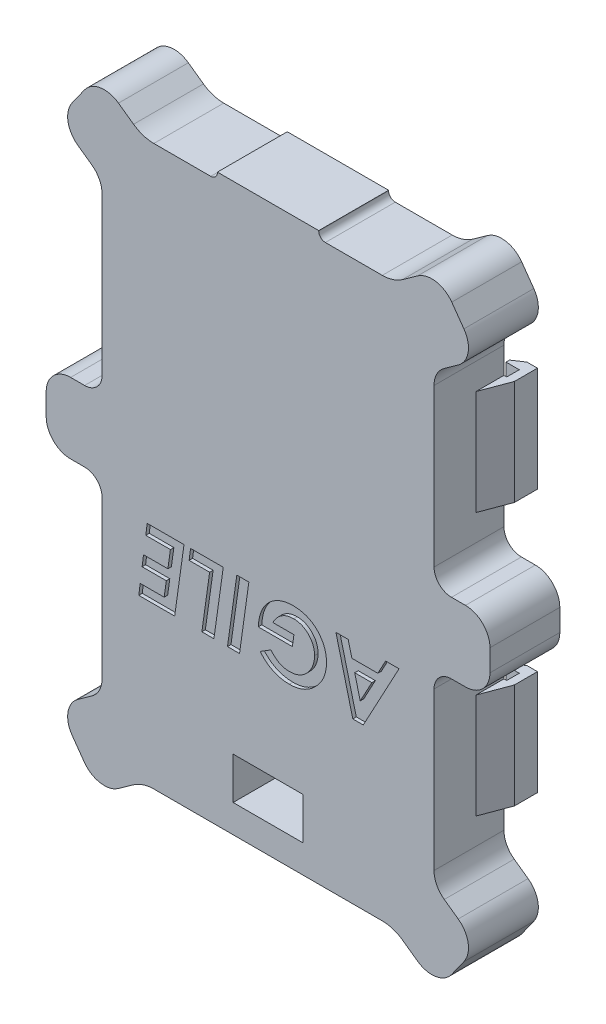
SolidWorks part; units mm, degrees
ref_plane "Front Plane" through (0, 0, 0) normal (0, 0, 1) x (1, 0, 0)
ref_plane "Top Plane" through (0, 0, 0) normal (0, 1, 0) x (1, 0, 0)
ref_plane "Right Plane" through (0, 0, 0) normal (1, 0, 0) x (0, 0, -1)
sketch "Sketch1" plane through (0, 0, 0) normal (0, 0, 1) x (1, 0, 0)
  line L0 (31.9975, -110.362) -> (31.9975, -120.362) construction
  line L1 (-24.4982, 18.6863) -> (-28.8129, 21.7633)
  line L2 (-42.0602, 15.2434) -> (-38.5765, 20.1284)
  line L3 (-36.4405, 2.638) -> (-40.4254, 5.4798)
  line L4 (-33.5049, -3.0612) -> (-33.5049, -48.0612)
  line L5 (-42.5049, -53.0612) -> (-38.5049, -53.0612)
  line L6 (43, -55.362) -> (43, -105.362) construction
  line L7 (-49.5049, -66.2828) -> (-49.5049, -60.0612)
  line L8 (-42.5049, -66.2828) -> (-42.5049, -71.7828) construction
  line L9 (0.9975, 17.328) -> (26.9975, 17.328)
  line L10 (70.5, -73.2828) -> (70.5, -71.7828) construction
  line L11 (77.5, -66.2828) -> (76, -66.2828) construction
  line L12 (70.5, -53.0612) -> (66.5, -53.0612)
  line L13 (61.5, -3.0612) -> (61.5, -48.0612)
  line L14 (64.4356, 2.638) -> (68.4204, 5.4798)
  line L15 (70.0553, 15.2434) -> (66.5716, 20.1284)
  line L16 (52.4933, 18.6863) -> (56.808, 21.7633)
  line L17 (-15.0049, -55.362) -> (-15.0049, -105.362) construction
  line L18 (52.4933, -145.0303) -> (56.808, -148.1073)
  line L19 (70.0553, -141.5874) -> (66.5716, -146.4724)
  line L20 (64.4356, -128.9821) -> (68.4204, -131.8238)
  line L21 (61.5, -123.2828) -> (61.5, -78.2828)
  line L22 (70.5, -73.2828) -> (66.5, -73.2828)
  line L23 (76, -66.2828) -> (76, -60.0612) construction
  line L24 (46.6871, -143.172) -> (-18.692, -143.172)
  line L25 (-42.5049, -66.2828) -> (-48.0049, -66.2828) construction
  line L26 (-42.5049, -73.2828) -> (-38.5049, -73.2828)
  line L27 (-33.5049, -123.2828) -> (-33.5049, -78.2828)
  line L28 (-36.4405, -128.9821) -> (-40.4254, -131.8238)
  line L29 (-42.0602, -141.5874) -> (-38.5765, -146.4724)
  line L30 (-24.4957, -145.0285) -> (-28.8129, -148.1073)
  line L31 (13.9975, -143.172) -> (13.9975, -125.172) construction
  line L32 (68.4204, 5.4798) -> (64.3561, 11.179) construction
  line L33 (33.9975, -34.362) -> (28.9975, -34.362) construction
  line L34 (28.9975, -34.362) -> (28.9975, -29.362) construction
  line L35 (-6.0025, 10.638) -> (-6.0025, -34.362) construction
  line L36 (33.9975, -34.362) -> (33.9975, -39.362) construction
  line L37 (33.9975, 10.638) -> (33.9975, -34.362) construction
  line L38 (30.3975, 16.828) -> (46.6871, 16.828)
  line L39 (26.9975, -39.362) -> (0.9975, -39.362) construction
  line L40 (26.9975, 18.828) -> (0.9975, 18.828)
  line L41 (64.3561, 11.179) -> (70.0553, 15.2434) construction
  line L42 (66.5716, 20.1284) -> (60.8724, 16.0641) construction
  line L43 (-6.0025, -34.362) -> (-6.0025, -50.362) construction
  line L44 (-6.0025, -50.362) -> (33.9975, -50.362) construction
  line L45 (33.9975, -50.362) -> (33.9975, -34.362) construction
  line L46 (31.9975, -50.362) -> (-4.0025, -50.362) construction
  line L47 (43, -55.362) -> (33.9975, -55.362) construction
  line L48 (26.9975, -48.362) -> (26.9975, -39.362) construction
  line L49 (-15.0049, -55.362) -> (-6.0025, -55.362) construction
  line L50 (0.9975, -48.362) -> (0.9975, -39.362) construction
  line L51 (31.9975, -110.362) -> (-4.0025, -110.362) construction
  line L52 (33.9975, -105.362) -> (43, -105.362) construction
  line L53 (31.9975, -120.362) -> (-4.0025, -120.362) construction
  line L54 (-6.0025, -34.362) -> (-1.0025, -34.362) construction
  line L55 (-4.0025, -120.362) -> (-4.0025, -110.362) construction
  line L56 (-1.0025, -34.362) -> (-1.0025, -29.362) construction
  line L57 (33.9975, 10.638) -> (28.9975, 10.638) construction
  line L58 (-6.0025, -105.362) -> (-15.0049, -105.362) construction
  line L59 (28.9975, 10.638) -> (28.9975, 5.638) construction
  line L60 (-6.0025, 10.638) -> (-1.0025, 10.638) construction
  line L61 (-1.0025, 10.638) -> (-1.0025, 5.638) construction
  line L62 (33.9975, -1.362) -> (33.9975, -22.362) construction
  line L63 (26.9975, -29.362) -> (0.9975, -29.362) construction
  line L64 (-6.0025, -22.362) -> (-6.0025, -1.362) construction
  line L65 (0.9975, 5.638) -> (26.9975, 5.638) construction
  line L66 (27.4975, -143.172) -> (0.4975, -143.172) construction
  line L67 (0.4975, -143.172) -> (0.4975, -136.172) construction
  line L68 (0.4975, -136.172) -> (27.4975, -136.172) construction
  line L69 (0.4975, -136.172) -> (0.4975, -125.172) construction
  line L70 (0.4975, -125.172) -> (27.4975, -125.172) construction
  line L71 (27.4975, -125.172) -> (27.4975, -136.172) construction
  line L72 (26.9975, -112.362) -> (26.9975, -120.362) construction
  line L73 (61.5, -78.2828) -> (43, -78.2828) construction
  line L74 (0.9975, -120.362) -> (0.9975, -112.362) construction
  line L75 (0.4975, -143.172) -> (0.4975, -113.172) construction
  line L76 (0.4975, -113.172) -> (27.4975, -113.172) construction
  line L77 (27.4975, -125.172) -> (24.4975, -125.172) construction
  line L78 (24.4975, -125.172) -> (24.4975, -134.172) construction
  line L79 (24.4975, -134.172) -> (3.4975, -134.172) construction
  line L80 (3.4975, -134.172) -> (3.4975, -125.172) construction
  line L81 (24.4975, -125.172) -> (24.4975, -134.172) construction
  line L82 (24.4975, -134.172) -> (3.4975, -134.172) construction
  line L83 (3.4975, -134.172) -> (3.4975, -125.172) construction
  line L84 (3.4975, -125.172) -> (0.9975, -120.362) construction
  line L85 (26.9975, -120.362) -> (24.4975, -125.172) construction
  line L86 (55.25, -78.2828) -> (49.25, -78.2828) construction
  line L87 (49.25, -78.2828) -> (49.25, -88.2828) construction
  line L88 (49.25, -88.2828) -> (55.25, -88.2828) construction
  line L89 (55.25, -88.2828) -> (55.25, -78.2828) construction
  line L90 (-15.0049, -78.2828) -> (-33.5049, -78.2828) construction
  line L91 (-21.2549, -78.2828) -> (-27.2549, -78.2828) construction
  line L92 (-27.2549, -78.2828) -> (-27.2549, -88.2828) construction
  line L93 (-27.2549, -88.2828) -> (-21.2549, -88.2828) construction
  line L94 (-21.2549, -88.2828) -> (-21.2549, -78.2828) construction
  line L95 (61.5, -3.0612) -> (43, -3.0612) construction
  line L96 (43, -3.0612) -> (43, -55.362) construction
  line L97 (55.25, -3.0612) -> (49.25, -3.0612) construction
  line L98 (49.25, -3.0612) -> (49.25, -13.0612) construction
  line L99 (49.25, -13.0612) -> (55.25, -13.0612) construction
  line L100 (55.25, -13.0612) -> (55.25, -3.0612) construction
  line L101 (-33.5049, -3.0612) -> (-15.0049, -3.0612) construction
  line L102 (-15.0049, -3.0612) -> (-15.0049, -55.362) construction
  line L103 (-21.2549, -3.0612) -> (-27.2549, -3.0612) construction
  line L104 (-27.2549, -3.0612) -> (-27.2549, -13.0612) construction
  line L105 (-27.2549, -13.0612) -> (-21.2549, -13.0612) construction
  line L106 (-21.2549, -13.0612) -> (-21.2549, -3.0612) construction
  line L107 (13.9975, -143.172) -> (13.9975, -135.172) construction
  line L108 (23.9975, -135.172) -> (3.9975, -135.172)
  line L109 (3.9975, -135.172) -> (3.9975, -123.172)
  line L110 (3.9975, -123.172) -> (23.9975, -123.172)
  line L111 (23.9975, -123.172) -> (23.9975, -135.172)
  line L112 (60.8724, -142.4081) -> (57.679, -146.886) construction
  line L113 (60.8724, -142.4081) -> (65.3503, -145.6015) construction
  line L114 (64.3561, -137.523) -> (68.4204, -131.8238) construction
  line L115 (64.3561, -137.523) -> (67.5495, -133.0451) construction
  line L116 (64.3561, -137.523) -> (68.8341, -140.7164) construction
  line L117 (65.3503, -145.6015) -> (68.8341, -140.7164)
  line L118 (52.4933, -145.0303) -> (54.501, -142.2149) construction
  line L119 (57.679, -146.886) -> (53.3642, -143.809)
  line L120 (46.6871, -143.172) -> (46.6871, -141.672) construction
  line L121 (46.6871, -141.672) -> (-18.6951, -141.672)
  line L122 (-18.692, -143.172) -> (-18.6951, -141.672) construction
  line L123 (-28.8129, -148.1073) -> (-40.4254, -131.8238) construction
  line L124 (-38.5765, -146.4724) -> (-32.8773, -142.4081) construction
  line L125 (-42.0602, -141.5874) -> (-36.361, -137.523) construction
  line L126 (-32.8773, -142.4081) -> (-29.6839, -146.886) construction
  line L127 (-32.8773, -142.4081) -> (-37.3552, -145.6015) construction
  line L128 (-36.361, -137.523) -> (-40.839, -140.7164) construction
  line L129 (-36.361, -137.523) -> (-39.5544, -133.0451) construction
  line L130 (-37.3552, -145.6015) -> (-40.839, -140.7164)
  line L131 (-29.6839, -146.886) -> (-25.3666, -143.8072)
  line L132 (-24.4957, -145.0285) -> (-25.3666, -143.8072) construction
  line L133 (-36.4405, -128.9821) -> (-35.5696, -130.2033) construction
  line L134 (-39.5544, -133.0451) -> (-35.5696, -130.2033)
  line L135 (-33.5049, -123.2828) -> (-32.0049, -123.2828) construction
  line L136 (-32.0049, -123.2828) -> (-32.0049, -78.2828)
  line L137 (-42.5049, -73.2828) -> (-42.5049, -53.0612) construction
  line L138 (-49.5049, -60.0612) -> (-42.5049, -60.0612) construction
  line L139 (-49.5049, -66.2828) -> (-42.5049, -66.2828) construction
  line L140 (-42.5049, -60.0612) -> (-42.5049, -54.5612) construction
  line L141 (-48.0049, -66.2828) -> (-48.0049, -60.0612)
  line L142 (-38.5049, -71.7828) -> (-42.5049, -71.7828)
  line L143 (-38.5049, -54.5612) -> (-42.5049, -54.5612) construction
  line L144 (-33.5049, -48.0612) -> (-32.0049, -48.0612)
  line L145 (-33.5049, -3.0612) -> (-32.0049, -3.0612)
  line L146 (-32.0049, -48.0612) -> (-32.0049, -3.0612)
  line L147 (-40.4254, 5.4798) -> (-36.361, 11.179) construction
  line L148 (-36.361, 11.179) -> (-42.0602, 15.2434) construction
  line L149 (-28.8129, 21.7633) -> (-32.8773, 16.0641) construction
  line L150 (-32.8773, 16.0641) -> (-38.5765, 20.1284) construction
  line L151 (-36.361, 11.179) -> (-38.0623, 8.7933) construction
  line L152 (-42.0602, 15.2434) -> (-40.839, 14.3724) construction
  line L153 (-40.4254, 5.4798) -> (-39.5544, 6.701) construction
  line L154 (-38.5765, 20.1284) -> (-37.3552, 19.2575) construction
  line L155 (-28.8129, 21.7633) -> (-29.6839, 20.542) construction
  line L156 (-36.4405, 2.638) -> (-35.5696, 3.8593) construction
  line L157 (-35.5696, 3.8593) -> (-39.5544, 6.701)
  line L158 (-40.839, 14.3724) -> (-37.3552, 19.2575)
  line L159 (-42.5049, -54.5612) -> (-38.5049, -54.5612)
  line L160 (-24.4982, 18.6863) -> (-25.3691, 17.465) construction
  line L161 (-29.6839, 20.542) -> (-25.3691, 17.465)
  line L162 (-18.692, 16.828) -> (-18.692, 15.328) construction
  line L163 (-18.692, 15.328) -> (0.9975, 15.328)
  line L164 (0.9975, 15.328) -> (0.9975, 17.328)
  line L165 (26.9975, 17.328) -> (26.9975, 15.328)
  line L166 (26.9975, 15.328) -> (46.6871, 15.328)
  line L167 (60.8724, 16.0641) -> (56.808, 21.7633) construction
  line L168 (-18.692, 16.828) -> (-2.4025, 16.828)
  line L169 (-0.5025, 18.728) -> (-0.5025, 18.828)
  line L170 (-0.5025, 18.828) -> (0.9975, 18.828)
  line L171 (28.4975, 18.728) -> (28.4975, 18.828)
  line L172 (28.4975, 18.828) -> (26.9975, 18.828)
  line L173 (64.3561, 11.179) -> (68.8341, 14.3724) construction
  line L174 (68.8341, 14.3724) -> (65.3503, 19.2575) construction
  line L175 (52.4933, 18.6863) -> (53.3642, 17.465) construction
  line L176 (57.679, 20.542) -> (53.3642, 17.465)
  line L177 (64.4356, 2.638) -> (63.5647, 3.8593) construction
  line L178 (63.5647, 3.8593) -> (67.5495, 6.701) construction
  line L179 (63.5647, 3.8593) -> (67.5495, 6.701)
  line L180 (67.5495, -133.0451) -> (63.5647, -130.2033) construction
  line L181 (61.5, -123.2828) -> (60, -123.2828) construction
  line L182 (60, -123.2828) -> (60, -78.2828)
  line L183 (66.5, -73.2828) -> (66.5, -71.7828) construction
  line L184 (66.5, -53.0612) -> (66.5, -54.5612) construction
  line L185 (61.5, -48.0612) -> (60, -48.0612) construction
  line L186 (61.5, -3.0612) -> (60, -3.0612) construction
  line L187 (77.5, -66.2828) -> (77.5, -60.0612)
  line L188 (76, -60.0612) -> (77.5, -60.0612) construction
  line L189 (70.5, -53.0612) -> (70.5, -54.5612) construction
  line L190 (66.5, -71.7828) -> (70.5, -71.7828)
  line L191 (76, -66.2828) -> (76, -60.0612)
  line L192 (70.5, -54.5612) -> (66.5, -54.5612)
  line L193 (60, -48.0612) -> (60, -3.0612)
  line L194 (76, -66.2828) -> (70.5, -66.2828) construction
  line L195 (70.5, -66.2828) -> (70.5, -71.7828) construction
  line L196 (76, -60.0612) -> (70.5, -60.0612) construction
  line L197 (70.5, -60.0612) -> (70.5, -54.5612) construction
  line L198 (67.5495, -133.0451) -> (63.5647, -130.2033)
  line L199 (68.8341, 14.3724) -> (65.3503, 19.2575)
  line L200 (3.9975, -123.172) -> (23.9975, -135.172) construction
  line L201 (23.9975, -123.172) -> (3.9975, -135.172) construction
  line L203 (1.9975, -136.672) -> (25.9975, -136.672)
  line L204 (1.9975, -136.672) -> (1.9975, -121.672)
  line L205 (1.9975, -121.672) -> (25.9975, -121.672)
  line L206 (25.9975, -136.672) -> (25.9975, -121.672)
  line L207 (1.9975, -136.672) -> (25.9975, -121.672) construction
  line L208 (1.9975, -121.672) -> (25.9975, -136.672) construction
  circle A0 centre (-37.998, 16.0311) radius 1 construction
  circle A1 centre (-29.6584, 17.5638) radius 1 construction
  circle A2 centre (-36.7303, 7.6471) radius 1 construction
  arc A3 (-38.5049, -53.0612) -> (-33.5049, -48.0612) centre (-38.5049, -48.0612) ccw
  arc A4 (-49.5049, -60.0612) -> (-42.5049, -53.0612) centre (-42.5049, -60.0612) cw
  circle A5 centre (-28.3907, 9.1798) radius 1 construction
  circle A6 centre (-33.1943, 12.6054) radius 3.5 construction
  arc A7 (-24.4982, 18.6863) -> (-18.692, 16.828) centre (-18.692, 26.828) ccw
  arc A8 (-40.4254, 5.4798) -> (-42.0602, 15.2434) centre (-36.361, 11.179) cw
  arc A9 (-38.5765, 20.1284) -> (-28.8129, 21.7633) centre (-32.8773, 16.0641) cw
  arc A10 (-33.5049, -3.0612) -> (-36.4405, 2.638) centre (-40.5049, -3.0612) ccw
  arc A11 (61.5, -3.0612) -> (64.4356, 2.638) centre (68.5, -3.0612) cw
  arc A12 (66.5716, 20.1284) -> (56.808, 21.7633) centre (60.8724, 16.0641) ccw
  arc A13 (68.4204, 5.4798) -> (70.0553, 15.2434) centre (64.3561, 11.179) ccw
  arc A14 (52.4933, 18.6863) -> (46.6871, 16.828) centre (46.6871, 26.828) cw
  circle A15 centre (61.1894, 12.6054) radius 3.5 construction
  circle A16 centre (56.3858, 9.1798) radius 1 construction
  arc A17 (77.5, -60.0612) -> (70.5, -53.0612) centre (70.5, -60.0612) ccw
  arc A18 (66.5, -53.0612) -> (61.5, -48.0612) centre (66.5, -48.0612) cw
  circle A19 centre (64.7254, 7.6471) radius 1 construction
  circle A20 centre (57.6534, 17.5638) radius 1 construction
  circle A21 centre (65.9931, 16.0311) radius 1 construction
  circle A22 centre (65.9931, -142.3751) radius 1 construction
  circle A23 centre (57.6534, -143.9078) radius 1 construction
  circle A24 centre (64.7254, -133.9911) radius 1 construction
  arc A25 (66.5, -73.2828) -> (61.5, -78.2828) centre (66.5, -78.2828) ccw
  arc A26 (77.5, -66.2828) -> (70.5, -73.2828) centre (70.5, -66.2828) cw
  circle A27 centre (56.3858, -135.5238) radius 1 construction
  circle A28 centre (61.1894, -138.9495) radius 3.5 construction
  arc A29 (52.4933, -145.0303) -> (46.6871, -143.172) centre (46.6871, -153.172) ccw construction
  arc A30 (68.4204, -131.8238) -> (70.0553, -141.5874) centre (64.3561, -137.523) cw
  arc A31 (66.5716, -146.4724) -> (56.808, -148.1073) centre (60.8724, -142.4081) cw
  arc A32 (61.5, -123.2828) -> (64.4356, -128.9821) centre (68.5, -123.2828) ccw
  arc A33 (-33.5049, -123.2828) -> (-36.4405, -128.9821) centre (-40.5049, -123.2828) cw
  arc A34 (-38.5765, -146.4724) -> (-28.8129, -148.1073) centre (-32.8773, -142.4081) ccw
  arc A35 (-40.4254, -131.8238) -> (-42.0602, -141.5874) centre (-36.361, -137.523) ccw
  arc A36 (-24.4957, -145.0285) -> (-18.692, -143.172) centre (-18.692, -153.172) cw
  circle A37 centre (-33.164, -138.172) radius 3.5 construction
  circle A38 centre (-28.3907, -135.5238) radius 1 construction
  arc A39 (-49.5049, -66.2828) -> (-42.5049, -73.2828) centre (-42.5049, -66.2828) ccw
  arc A40 (-38.5049, -73.2828) -> (-33.5049, -78.2828) centre (-38.5049, -78.2828) cw
  circle A41 centre (-36.7303, -133.9911) radius 1 construction
  circle A42 centre (-29.6584, -143.9078) radius 1 construction
  circle A43 centre (-37.998, -142.3751) radius 1 construction
  circle A44 centre (-6.0025, -34.362) radius 1.5 construction
  circle A45 centre (55.31, -25.5612) radius 1.5 construction
  circle A46 centre (33.9975, -136.982) radius 1.5 construction
  circle A47 centre (-6.0025, -136.982) radius 1.5 construction
  circle A48 centre (-6.0025, 10.638) radius 1.5 construction
  circle A49 centre (33.9975, 10.638) radius 1.5 construction
  circle A50 centre (33.9975, -34.362) radius 1.5 construction
  circle A51 centre (31.9975, -50.362) radius 1.5 construction
  circle A52 centre (-4.0025, -50.362) radius 1.5 construction
  arc A53 (-6.0025, -55.362) -> (0.9975, -48.362) centre (-6.0025, -48.362) ccw construction
  arc A54 (33.9975, -55.362) -> (26.9975, -48.362) centre (33.9975, -48.362) cw construction
  circle A55 centre (-4.0025, -110.362) radius 1.5 construction
  circle A56 centre (31.9975, -110.362) radius 1.5 construction
  arc A57 (0.9975, -112.362) -> (-6.0025, -105.362) centre (-6.0025, -112.362) ccw construction
  arc A58 (33.9975, -105.362) -> (26.9975, -112.362) centre (33.9975, -112.362) ccw construction
  arc A59 (33.9975, -22.362) -> (26.9975, -29.362) centre (26.9975, -22.362) cw construction
  circle A60 centre (-27.3149, -25.5612) radius 1.5 construction
  circle A61 centre (55.31, -100.7828) radius 1.5 construction
  circle A62 centre (-27.3149, -100.7828) radius 1.5 construction
  arc A63 (0.9975, -29.362) -> (-6.0025, -22.362) centre (0.9975, -22.362) cw construction
  arc A64 (-6.0025, -1.362) -> (0.9975, 5.638) centre (0.9975, -1.362) cw construction
  arc A65 (33.9975, -1.362) -> (26.9975, 5.638) centre (26.9975, -1.362) ccw construction
  circle A66 centre (27.4975, -136.172) radius 1 construction
  circle A67 centre (0.4975, -136.172) radius 1 construction
  circle A68 centre (27.4975, -125.172) radius 1 construction
  circle A69 centre (0.4975, -125.172) radius 1 construction
  arc A70 (53.3642, -143.809) -> (46.6871, -141.672) centre (46.6871, -153.172) ccw
  arc A71 (57.679, -146.886) -> (65.3503, -145.6015) centre (60.8724, -142.4081) ccw
  arc A72 (52.4933, -145.0303) -> (46.6871, -143.172) centre (46.6871, -153.172) ccw
  arc A73 (63.5647, -130.2033) -> (60, -123.2828) centre (68.5, -123.2828) cw
  circle A74 centre (-40.7503, -63.172) radius 3.5 construction
  circle A75 centre (-46.6503, -63.172) radius 1 construction
  circle A76 centre (-34.8503, -63.172) radius 1 construction
  circle A77 centre (-40.4873, -69.2563) radius 1 construction
  circle A78 centre (-40.4873, -57.0877) radius 1 construction
  circle A79 centre (68.4824, -57.0877) radius 1 construction
  circle A80 centre (68.4824, -69.2563) radius 1 construction
  circle A81 centre (62.8454, -63.172) radius 1 construction
  circle A82 centre (74.6454, -63.172) radius 1 construction
  circle A83 centre (68.7454, -63.172) radius 3.5 construction
  arc A84 (-37.3552, -145.6015) -> (-29.6839, -146.886) centre (-32.8773, -142.4081) ccw
  arc A85 (-18.6951, -141.672) -> (-25.3666, -143.8072) centre (-18.6951, -153.1623) ccw
  arc A86 (-40.839, -140.7164) -> (-39.5544, -133.0451) centre (-36.361, -137.523) cw
  arc A87 (-35.5696, -130.2033) -> (-32.0049, -123.2828) centre (-40.5049, -123.2828) ccw
  arc A88 (-32.0049, -78.2828) -> (-38.5049, -71.7828) centre (-38.5049, -78.2828) ccw
  arc A89 (-42.5049, -71.7828) -> (-48.0049, -66.2828) centre (-42.5049, -66.2828) cw
  arc A90 (-48.0049, -60.0612) -> (-42.5049, -54.5612) centre (-42.5049, -60.0612) cw
  arc A91 (-32.0049, -48.0612) -> (-38.5049, -54.5612) centre (-38.5049, -48.0612) cw
  arc A92 (-32.0049, -3.0612) -> (-35.5696, 3.8593) centre (-40.5049, -3.0612) ccw
  arc A93 (-39.5544, 6.701) -> (-40.839, 14.3724) centre (-36.361, 11.179) cw
  arc A94 (-37.3552, 19.2575) -> (-29.6839, 20.542) centre (-32.8773, 16.0641) cw
  arc A95 (-25.3691, 17.465) -> (-18.692, 15.328) centre (-18.692, 26.828) ccw
  arc A96 (30.3975, 16.828) -> (28.4975, 18.728) centre (30.3975, 18.728) cw
  arc A97 (-0.5025, 18.728) -> (-2.4025, 16.828) centre (-2.4025, 18.728) cw
  arc A98 (67.5495, 6.701) -> (68.8341, 14.3724) centre (64.3561, 11.179) ccw
  arc A99 (65.3503, 19.2575) -> (57.679, 20.542) centre (60.8724, 16.0641) ccw
  arc A100 (46.6871, 15.328) -> (53.3642, 17.465) centre (46.6871, 26.828) ccw
  arc A101 (67.5495, -133.0451) -> (68.8341, -140.7164) centre (64.3561, -137.523) cw
  arc A102 (63.5647, 3.8593) -> (60, -3.0612) centre (68.5, -3.0612) ccw
  arc A103 (66.5, -54.5612) -> (60, -48.0612) centre (66.5, -48.0612) cw
  arc A104 (76, -60.0612) -> (70.5, -54.5612) centre (70.5, -60.0612) ccw
  arc A105 (76, -66.2828) -> (70.5, -71.7828) centre (70.5, -66.2828) cw
  arc A106 (66.5, -71.7828) -> (60, -78.2828) centre (66.5, -78.2828) ccw
  point P25 (-34.5122, 25.8276)
  point P29 (-34.5122, 25.8276)
  point P64 (62.5072, 25.8276)
  point P95 (62.5072, -152.1716)
  point P124 (-34.5122, -152.1716)
  point P144 (13.9975, 16.828)
  point P147 (13.9975, 16.828)
  point P154 (13.9975, -50.362)
  point P182 (13.9975, -125.172)
  point P196 (33.9975, -29.362)
  point P199 (-6.0025, -29.362)
  point P202 (-6.0025, 5.638)
  point P215 (33.9975, 5.638)
  point P229 (13.9975, -143.172)
  point P249 (52.25, -78.2828)
  point P256 (-24.2549, -78.2828)
  point P261 (52.25, -3.0612)
  point P267 (-24.2549, -3.0612)
  point P273 (13.9975, -135.172)
  point P358 (13.9975, -129.172)
  dimension "D6" = 7
  dimension "D7" = 7
  dimension "D10" = 6.7223
  dimension "D11" = 1.9
  dimension "D1" = 10
  dimension "D2" = 7
  dimension "D3" = 7
  dimension "D4" = 5
  dimension "D5" = 7
  dimension "D8" = 7
  dimension "D9" = 5.4953
extrude "Бобышка-Вытянуть3" add sketch "Sketch1" along normal blind 18 contours L190 A106 L182 A73 L198 A101 L117 A71 L119 A70 L121 A85 L131 A84 L130 A86 L134 A87 L136 A88 L142 A89 L141 A90 L159 A91 L144 A3 L5 A4 L7 A39 L26 A40 L27 A33 L28 A35 L29 A34 L30 A36 L24 A72 L18 A31 L19 A30 L20 A32 L21 | L144 L146 L145 L4 | L203 L206 L205 L204 L110 L111 L108 L109 region at (-21.8054, 17.0999, 0) region at (-32.7549, -25.5612, 0) region at (2.2806, -129.172, 0)
sketch "Эскиз1" plane through (0, 0, 18) normal (0, 0, 1) x (1, 0, 0)
  line L0 (66.5, -53.0612) -> (70.5, -53.0612)
  line L6 (3.9975, -135.172) -> (23.9975, -135.172)
  line L7 (3.9975, -135.172) -> (3.9975, -123.172)
  line L8 (3.9975, -123.172) -> (23.9975, -123.172)
  line L10 (23.9975, -135.172) -> (23.9975, -123.172)
  line L11 (3.9975, -135.172) -> (23.9975, -123.172) construction
  line L12 (3.9975, -123.172) -> (23.9975, -135.172) construction
  line L25 (46.6871, -141.672) -> (-18.6951, -141.672)
  line L30 (61.5, -123.2828) -> (61.5, -78.2828)
  line L31 (66.5, -73.2828) -> (70.5, -73.2828)
  line L32 (77.5, -66.2828) -> (77.5, -60.0612)
  line L35 (61.5, -48.0612) -> (61.5, -3.0612)
  line L36 (64.4356, 2.638) -> (68.4204, 5.4798)
  line L37 (70.0553, 15.2434) -> (66.5716, 20.1284)
  line L38 (56.808, 21.7633) -> (52.4933, 18.6863)
  line L39 (46.6871, 16.828) -> (30.3975, 16.828)
  line L40 (28.4975, 18.828) -> (-0.5025, 18.828)
  line L41 (-0.5025, 18.828) -> (-0.5025, 18.728)
  line L42 (28.4975, 18.728) -> (28.4975, 18.828)
  line L43 (-2.4025, 16.828) -> (-18.692, 16.828)
  line L44 (-24.4982, 18.6863) -> (-28.8129, 21.7633)
  line L45 (-38.5765, 20.1284) -> (-42.0602, 15.2434)
  line L46 (-40.4254, 5.4798) -> (-36.4405, 2.638)
  line L47 (-33.5049, -3.0612) -> (-33.5049, -48.0612)
  line L48 (-38.5049, -53.0612) -> (-42.5049, -53.0612)
  line L49 (-49.5049, -60.0612) -> (-49.5049, -66.2828)
  line L50 (-42.5049, -73.2828) -> (-38.5049, -73.2828)
  line L51 (-33.5049, -78.2828) -> (-33.5049, -123.2828)
  line L52 (-36.4405, -128.9821) -> (-40.4254, -131.8238)
  line L53 (-42.0602, -141.5874) -> (-38.5765, -146.4724)
  line L54 (-28.8129, -148.1073) -> (-24.4957, -145.0285)
  line L55 (-18.692, -143.172) -> (46.6871, -143.172)
  line L56 (56.808, -148.1073) -> (52.4933, -145.0303)
  line L57 (66.5716, -146.4724) -> (70.0553, -141.5874)
  line L58 (68.4204, -131.8238) -> (64.4356, -128.9821)
  arc A2 (61.5, -123.2828) -> (64.4356, -128.9821) centre (68.5, -123.2828) ccw construction
  arc A3 (-33.5049, -78.2828) -> (-38.5049, -73.2828) centre (-38.5049, -78.2828) ccw construction
  arc A4 (70.0553, -141.5874) -> (68.4204, -131.8238) centre (64.3561, -137.523) ccw
  arc A5 (-42.0602, -141.5874) -> (-40.4254, -131.8238) centre (-36.361, -137.523) cw
  arc A6 (-36.4405, -128.9821) -> (-33.5049, -123.2828) centre (-40.5049, -123.2828) ccw
  arc A7 (56.808, -148.1073) -> (66.5716, -146.4724) centre (60.8724, -142.4081) ccw
  arc A8 (46.6871, -143.172) -> (52.4933, -145.0303) centre (46.6871, -153.172) cw
  arc A9 (-38.5765, -146.4724) -> (-28.8129, -148.1073) centre (-32.8773, -142.4081) ccw
  arc A10 (-24.4957, -145.0285) -> (-18.692, -143.172) centre (-18.692, -153.172) cw
  arc A11 (64.4356, -128.9821) -> (61.5, -123.2828) centre (68.5, -123.2828) cw
  arc A12 (61.5, -78.2828) -> (66.5, -73.2828) centre (66.5, -78.2828) cw
  arc A13 (70.5, -73.2828) -> (77.5, -66.2828) centre (70.5, -66.2828) ccw
  arc A14 (77.5, -60.0612) -> (70.5, -53.0612) centre (70.5, -60.0612) ccw
  arc A15 (66.5, -53.0612) -> (61.5, -48.0612) centre (66.5, -48.0612) cw
  arc A16 (61.5, -3.0612) -> (64.4356, 2.638) centre (68.5, -3.0612) cw
  arc A17 (68.4204, 5.4798) -> (70.0553, 15.2434) centre (64.3561, 11.179) ccw
  arc A18 (66.5716, 20.1284) -> (56.808, 21.7633) centre (60.8724, 16.0641) ccw
  arc A19 (52.4933, 18.6863) -> (46.6871, 16.828) centre (46.6871, 26.828) cw
  arc A20 (28.4975, 18.728) -> (30.3975, 16.828) centre (30.3975, 18.728) ccw
  arc A21 (-18.692, 16.828) -> (-24.4982, 18.6863) centre (-18.692, 26.828) cw
  arc A22 (-2.4025, 16.828) -> (-0.5025, 18.728) centre (-2.4025, 18.728) ccw
  arc A23 (-38.5765, 20.1284) -> (-28.8129, 21.7633) centre (-32.8773, 16.0641) cw
  arc A24 (-42.0602, 15.2434) -> (-40.4254, 5.4798) centre (-36.361, 11.179) ccw
  arc A25 (-36.4405, 2.638) -> (-33.5049, -3.0612) centre (-40.5049, -3.0612) cw
  arc A26 (-49.5049, -60.0612) -> (-42.5049, -53.0612) centre (-42.5049, -60.0612) cw
  arc A27 (-38.5049, -53.0612) -> (-33.5049, -48.0612) centre (-38.5049, -48.0612) ccw
  arc A28 (-49.5049, -66.2828) -> (-42.5049, -73.2828) centre (-42.5049, -66.2828) ccw
  arc A29 (-38.5049, -73.2828) -> (-33.5049, -78.2828) centre (-38.5049, -78.2828) cw
  point P52 (13.9975, -129.172)
  point P53 (13.9975, -129.172)
extrude "Бобышка-Вытянуть4" add sketch "Эскиз1" along normal blind 2 contours L50 A29 L51 A6 L52 A5 L53 A9 L54 A10 L55 A8 L56 A7 L57 A4 L58 A11 L30 A12 L31 A13 L32 A14 L0 A15 L35 A16 L36 A17 L37 A18 L38 A19 L39 A20 L42 L40 L41 A22 L43 A21 L44 A23 L45 A24 L46 A25 region at (13.9975, -61.9149, 18)
sketch "Эскиз2" plane through (0, 0, 0) normal (0, 0, -1) x (-1, 0, 0)
  line L1 (-1.9975, -136.672) -> (-25.9975, -136.672)
  line L2 (-1.9975, -136.672) -> (-1.9975, -121.672)
  line L3 (-1.9975, -121.672) -> (-25.9975, -121.672)
  line L4 (-25.9975, -136.672) -> (-25.9975, -121.672)
  line L5 (-1.9975, -136.672) -> (-25.9975, -121.672) construction
  line L6 (-1.9975, -121.672) -> (-25.9975, -136.672) construction
  line L7 (-3.9975, -135.172) -> (-23.9975, -135.172)
  line L8 (-3.9975, -135.172) -> (-3.9975, -123.172)
  line L9 (-3.9975, -123.172) -> (-23.9975, -123.172)
  line L10 (-23.9975, -135.172) -> (-23.9975, -123.172)
  line L11 (-3.9975, -135.172) -> (-23.9975, -123.172) construction
  line L12 (-3.9975, -123.172) -> (-23.9975, -135.172) construction
  point P4 (-13.9975, -129.172)
  point P11 (-13.9975, -129.172)
extrude "Вырез-Вытянуть1" cut sketch "Эскиз2" against normal blind 6
sketch "Эскиз3" plane through (0, -143.172, 0) normal (0, -1, 0) x (1, 0, 0)
  line L0 (41.6975, 0) -> (44.2975, 0)
  line L1 (13.9975, 0.2) -> (13.9975, 4.2) construction
  line L2 (-3.0025, 4.2) -> (30.9975, 4.2)
  line L3 (30.9975, 4.2) -> (30.9975, 0)
  line L4 (30.9975, 0) -> (-3.0025, 0)
  line L5 (-3.0025, 0) -> (-3.0025, 4.2)
  line L6 (-3.0025, 0) -> (-15.0025, 0) construction
  line L7 (30.9975, 0) -> (42.9975, 0) construction
  line L8 (46.6871, 0) -> (-18.692, 0) construction
  line L9 (44.2975, 0) -> (44.2975, 4)
  line L10 (41.6975, 0) -> (41.6975, 4)
  line L12 (-16.3025, 0) -> (-13.7025, 0)
  line L15 (-13.7025, 0) -> (-13.7025, 4)
  line L16 (-16.3025, 0) -> (-16.3025, 4)
  arc A0 (41.6975, 4) -> (44.2975, 4) centre (42.9975, 4) cw
  arc A2 (-13.7025, 4) -> (-16.3025, 4) centre (-15.0025, 4) ccw
  point P9 (13.9975, 4.2)
  point P14 (42.9975, 0)
  point P21 (-15.0025, 0)
  point P22 (-12.1059, 2.6062)
extrude "Вырез-Вытянуть2" cut sketch "Эскиз3" against normal blind 1.5
sketch "Эскиз4" plane through (0, 0, 20) normal (0, 0, 1) x (1, 0, 0)
  line L0 (61.5, -78.2828) -> (-33.5049, -78.2828) construction
  arc A0 (-33.5049, -78.2828) -> (-38.5049, -73.2828) centre (-38.5049, -78.2828) ccw construction
  text T0 "AGILE" font "Century Gothic" height in points 72
extrude "Вырез-Вытянуть3" cut sketch "Эскиз4" against normal blind 1
sketch "Эскиз5" plane through (-33.5049, 0, 0) normal (-1, 0, 0) x (0, 0, 1)
  line L0 (0, -25.5612) -> (0, -40.5612) construction
  line L2 (0, -100.7828) -> (0, -115.7828) construction
  line L4 (0, -100.7828) -> (0, -85.7828) construction
  line L8 (0, -3.0612) -> (0, -48.0612) construction
  line L9 (0, -40.5612) -> (0, -10.5612) construction
  line L10 (8, -10.5612) -> (-3.2, -10.5612)
  line L12 (-3.2, -40.5612) -> (8, -40.5612)
  line L13 (8, -40.5612) -> (8, -10.5612)
  line L14 (0, -123.2828) -> (0, -78.2828) construction
  line L15 (-3.2, -40.5612) -> (-3.2, -10.5612) construction
  line L21 (0, -85.7828) -> (8, -85.7828)
  line L22 (8, -85.7828) -> (8, -115.7828)
  line L23 (8, -115.7828) -> (-3.2, -115.7828)
  line L24 (-3.2, -115.7828) -> (-3.2, -85.7828) construction
  line L25 (-3.2, -85.7828) -> (0, -85.7828)
  line L26 (-3.2, -85.7828) -> (-6.2, -85.7828) construction
  line L27 (-3.2, -85.7828) -> (-6.2, -85.7828)
  line L28 (-6.2, -85.7828) -> (-6.2, -115.7828)
  line L29 (-6.2, -115.7828) -> (-3.4965, -115.7828)
  line L30 (-3.2, -40.5612) -> (-6.6, -40.5612)
  line L31 (-6.6, -40.5612) -> (-6.6, -10.5612)
  line L32 (-6.6, -10.5612) -> (-3.2, -10.5612)
  point P0 (0, -25.5612)
  point P4 (0, -100.7828)
  line M25 (0, -3.0612) -> (0, -48.0612)
extrude "Бобышка-Вытянуть5" add sketch "Эскиз5" along normal blind 3 contours L12 L13 L10 M25 | L32 L31 L30 L12 L10 M25 region at (-33.5049, -25.5612, 4) region at (-33.5049, -25.5612, -3.3)
sketch "Эскиз7" plane through (-33.5049, 0, 0) normal (1, 0, 0) x (0, 0, -1)
  line L0 (6.6, -10.5612) -> (3.6, -10.5612) construction
  line L1 (0, -10.5612) -> (6.6, -10.5612) construction
  line L2 (3.6, -10.5612) -> (6.6, -10.5612)
  line L3 (6.6, -10.5612) -> (6.6, -40.5612)
  line L4 (6.6, -40.5612) -> (4.7, -40.5612)
  line L5 (6.6, -40.5612) -> (0, -40.5612) construction
  line L8 (3.6, -10.5612) -> (3.6, -40.5612)
  line L9 (3.6, -40.5612) -> (4.7, -40.5612)
extrude "Бобышка-Вытянуть6" add sketch "Эскиз7" along normal blind 3
sketch "Эскиз8" plane through (0, -10.5612, 0) normal (0, 1, 0) x (1, 0, 0)
  line L2 (-33.5049, 3.6) -> (-33.5049, 6.6) construction
  line L9 (-36.5049, -8) -> (-36.5049, 6.6) construction
  line L10 (-36.5049, 0) -> (-33.5049, -8)
  line L11 (-30.5049, 6.6) -> (-30.5049, 4.6)
  line L12 (-33.5049, -8) -> (-36.5049, -8)
  line L13 (-36.5049, -8) -> (-36.5049, 0)
  line L14 (-30.5049, 4.6) -> (-33.5049, 6.6)
  line L15 (-33.5049, 6.6) -> (-30.5049, 6.6)
  line L16 (-30.5049, 3.6) -> (-30.5049, 4.6) construction
  line L18 (-33.5049, 0) -> (-34.3049, 0)
  line L19 (-34.3049, 0) -> (-34.3049, 3.6)
  line L20 (-34.3049, 3.6) -> (-33.5049, 3.6)
  line L21 (-33.5049, 3.6) -> (-33.5049, 0)
sketch "Эскиз9" plane through (-33.5049, 0, 0) normal (-1, 0, 0) x (0, 0, 1)
  line L0 (0, -100.7828) -> (0, -115.7828) construction
  line L1 (0, -123.2828) -> (0, -78.2828) construction
  line L2 (0, -100.7828) -> (0, -85.7828) construction
  line L3 (0, -115.7828) -> (8, -115.7828)
  line L4 (8, -115.7828) -> (8, -85.7828)
  line L5 (8, -85.7828) -> (0, -85.7828)
  line L6 (0, -85.7828) -> (-6.6, -85.7828)
  line L7 (-6.6, -85.7828) -> (-6.6, -115.7828)
  line L8 (-6.6, -115.7828) -> (0, -115.7828)
extrude "Бобышка-Вытянуть7" add sketch "Эскиз9" along normal blind 3 separate body
sketch "Эскиз10" plane through (-33.5049, 0, 0) normal (1, 0, 0) x (0, 0, -1)
  line L0 (6.6, -115.7828) -> (-8, -115.7828) construction
  line L1 (6.6, -85.7828) -> (3.6, -85.7828)
  line L2 (6.6, -85.7828) -> (6.6, -115.7828)
  line L3 (6.6, -115.7828) -> (3.6, -115.7828)
  line L4 (3.6, -85.7828) -> (3.6, -115.7828)
  line L5 (6.6, -85.7828) -> (3.6, -115.7828) construction
  line L6 (6.6, -115.7828) -> (3.6, -85.7828) construction
  point P4 (5.1, -100.7828)
extrude "Бобышка-Вытянуть8" add sketch "Эскиз10" along normal blind 3
sketch "Эскиз11" plane through (0, -115.7828, 0) normal (0, -1, 0) x (1, 0, 0)
  line L0 (-33.5049, 8) -> (-36.5049, 0)
  line L1 (-30.5049, -3.6) -> (-30.5049, -6.6) construction
  line L2 (-36.5049, -6.6) -> (-36.5049, 8) construction
  line L3 (-36.5049, -6.6) -> (-30.5049, -6.6) construction
  line L4 (-33.5049, -6.6) -> (-30.5049, -4.6)
  line L7 (-33.5049, 8) -> (-36.5049, 8)
  line L8 (-36.5049, 8) -> (-36.5049, 0)
  line L9 (-33.5049, -6.6) -> (-30.5049, -6.6)
  line L10 (-30.5049, -6.6) -> (-30.5049, -4.6)
  line L11 (-33.5049, 0) -> (-34.3049, 0)
  line L12 (-33.5049, -3.6) -> (-34.3049, -3.6)
  line L13 (-34.3049, -3.6) -> (-34.3049, 0)
  line L15 (-33.5049, 0) -> (-33.5049, -3.6)
  line L16 (-30.5049, -3.6) -> (-30.5049, -4.6) construction
extrude "Вырез-Вытянуть5" cut sketch "Эскиз11" against normal blind 30
sketch "Эскиз12" plane through (61.5, 0, 0) normal (1, 0, 0) x (0, 0, -1)
  line L0 (0, -100.7828) -> (0, -115.7828) construction
  line L1 (0, -123.2828) -> (0, -78.2828) construction
  line L2 (0, -115.7828) -> (-8, -115.7828)
  line L3 (-8, -115.7828) -> (-8, -85.7828)
  line L4 (0, -115.7828) -> (6.6, -115.7828)
  line L5 (6.6, -115.7828) -> (6.6, -85.7828)
  line L6 (6.6, -85.7828) -> (-8, -85.7828)
extrude "Бобышка-Вытянуть9" add sketch "Эскиз12" along normal blind 3
sketch "Эскиз14" plane through (0, -115.7828, 0) normal (0, -1, 0) x (1, 0, 0)
  line L0 (61.5, -6.6) -> (61.5, -3.6)
  line L1 (61.5, 0) -> (61.5, -6.6) construction
  line L2 (61.5, -3.6) -> (58.5, -3.6)
  line L3 (58.5, -3.6) -> (58.5, -6.6)
  line L4 (58.5, -6.6) -> (61.5, -6.6)
extrude "Бобышка-Вытянуть10" add sketch "Эскиз14" against normal blind 30
sketch "Эскиз15" plane through (0, -115.7828, 0) normal (0, -1, 0) x (1, 0, 0)
  line L0 (61.5, -3.6) -> (61.5, -6.6) construction
  line L1 (64.5, -6.6) -> (58.5, -6.6) construction
  line L3 (64.5, 8) -> (64.5, -6.6) construction
  line L4 (61.5, 8) -> (64.5, 0)
  line L5 (58.5, -3.6) -> (58.5, -6.6) construction
  line L6 (58.5, -4.6) -> (61.5, -6.6)
  line L7 (61.5, -6.6) -> (58.5, -6.6)
  line L8 (58.5, -6.6) -> (58.5, -4.6)
  line L9 (64.5, 0) -> (64.5, 8)
  line L10 (64.5, 8) -> (61.5, 8)
  line L13 (58.5, -3.6) -> (58.5, -4.6) construction
  line L14 (61.5, 0) -> (62.3, 0)
  line L15 (62.3, 0) -> (62.3, -3.6)
  line L16 (62.3, -3.6) -> (61.5, -3.6)
  line L17 (61.5, -3.6) -> (61.5, 0)
  point P16 (61.5, 8)
  point P19 (64.5, 0)
  point P20 (58.5, -4.6)
  point P24 (64.5, 8)
  point P25 (58.5, -6.6)
  point P26 (61.5, -6.6)
sketch "Эскиз16" plane through (61.5, 0, 0) normal (1, 0, 0) x (0, 0, -1)
  line L0 (0, -25.5612) -> (0, -40.5612) construction
  line L1 (0, -3.0612) -> (0, -48.0612) construction
  line L2 (0, -25.5612) -> (0, -10.5612) construction
  line L3 (0, -40.5612) -> (-8, -40.5612)
  line L4 (-8, -40.5612) -> (-8, -10.5612)
  line L5 (-8, -10.5612) -> (0, -10.5612)
  line L6 (0, -10.5612) -> (6.6, -10.5612)
  line L7 (6.6, -10.5612) -> (6.6, -40.5612)
  line L8 (6.6, -40.5612) -> (0, -40.5612)
extrude "Бобышка-Вытянуть11" add sketch "Эскиз16" along normal blind 3
sketch "Эскиз17" plane through (0, -10.5612, 0) normal (0, 1, 0) x (1, 0, 0)
  line L1 (61.5, 6.6) -> (58.5, 6.6)
  line L2 (61.5, 6.6) -> (61.5, 3.6)
  line L3 (61.5, 3.6) -> (58.5, 3.6)
  line L4 (58.5, 6.6) -> (58.5, 3.6)
  line L5 (61.5, 6.6) -> (58.5, 3.6) construction
  line L6 (61.5, 3.6) -> (58.5, 6.6) construction
  point P4 (60, 5.1)
extrude "Бобышка-Вытянуть12" add sketch "Эскиз17" against normal blind 30
sketch "Эскиз18" plane through (0, -10.5612, 0) normal (0, 1, 0) x (1, 0, 0)
  line L0 (61.5, 0) -> (62.3, 0)
  line L2 (62.3, 0) -> (62.3, 3.6)
  line L3 (64.5, 6.6) -> (64.5, -8) construction
  line L8 (64.5, 0) -> (61.5, -8)
  line L9 (61.5, -8) -> (64.5, -8)
  line L10 (64.5, -8) -> (64.5, 0)
  line L11 (58.5, 3.6) -> (58.5, 4.6) construction
  line L12 (58.5, 6.6) -> (58.5, 3.6) construction
  line L13 (58.5, 4.6) -> (61.5, 6.6)
  line L14 (61.5, 6.6) -> (58.5, 6.6)
  line L15 (58.5, 6.6) -> (58.5, 4.6)
  line L16 (62.3, 3.6) -> (61.5, 3.6)
  line L17 (61.5, 3.6) -> (61.5, 0)
fillet "Скругление1" radius 1.5 4 edges at (3.9975, -129.172, 6) (23.9975, -129.172, 6) (13.9975, -135.172, 6) (13.9975, -123.172, 6)
extrude "Вырез-Вытянуть9" cut sketch "Эскиз8" against normal blind 30
extrude "Вырез-Вытянуть10" cut sketch "Эскиз15" against normal blind 30
extrude "Вырез-Вытянуть11" cut sketch "Эскиз18" against normal blind 30
